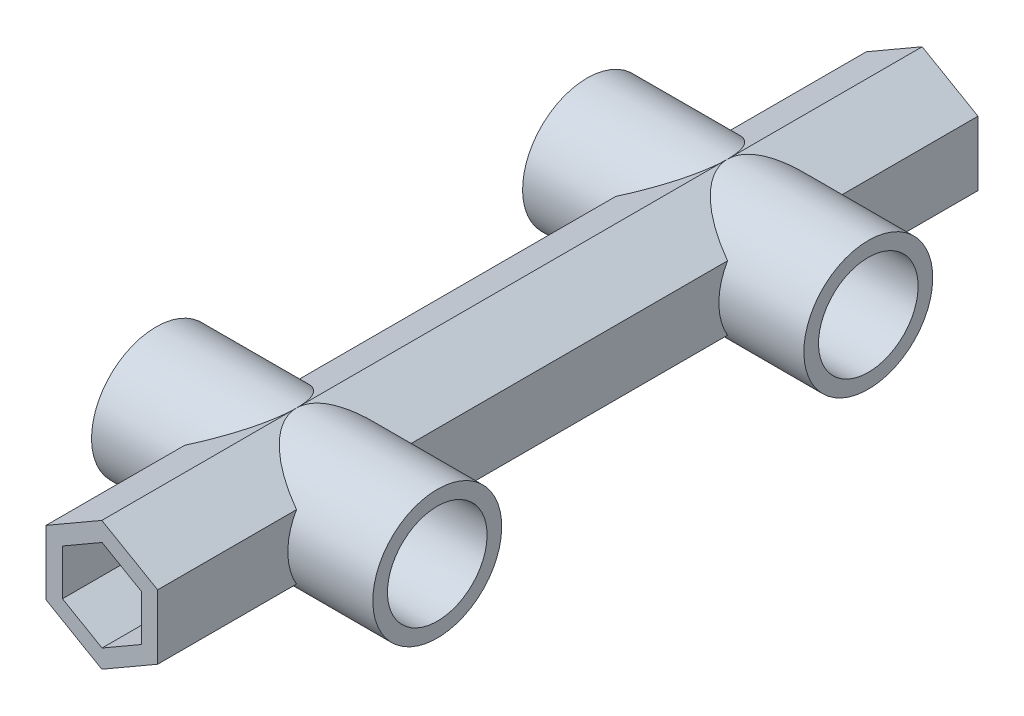
SolidWorks part; units mm, degrees
ref_plane "Front Plane" through (0, 0, 0) normal (0, 0, 1) x (1, 0, 0)
ref_plane "Top Plane" through (0, 0, 0) normal (0, 1, 0) x (1, 0, 0)
ref_plane "Right Plane" through (0, 0, 0) normal (1, 0, 0) x (0, 0, -1)
sketch "Sketch1" plane through (0, 0, 0) normal (0, 0, 1) x (1, 0, 0)
  line L1 (0, -11) -> (9.5263, -5.5)
  line L2 (9.5263, -5.5) -> (9.5263, 5.5)
  line L3 (9.5263, 5.5) -> (0, 11)
  line L4 (0, 11) -> (-9.5263, 5.5)
  line L5 (-9.5263, 5.5) -> (-9.5263, -5.5)
  line L6 (-9.5263, -5.5) -> (0, -11)
  circle A0 centre (0, 0) radius 11
  circle A1 centre (0, 0) radius 9.5263 construction
  circle A2 centre (0, 0) radius 6.4
  dimension "D1" = 22
  dimension "D2" = 12.8
extrude "Boss-Extrude1" [suppressed] add sketch "Sketch1" along normal mid plane 20 contours L4 A0 | L5 A0 | L5 L6 L1 L2 L3 L4 | L3 A0 | L2 A0 | L1 A0 | L6 A0
extrude "Boss-Extrude2" add sketch "Sketch1<3>" along normal mid plane 140 separate body contours L5 L6 L1 L2 L3 L4 A2 | A2 region at (-4.6176, -7.998, 0)
sketch "Sketch1<3>" plane through (0, 0, 0) normal (0, 0, 1) x (1, 0, 0) same geometry as "Sketch1"
sketch "Sketch10" plane through (0, 0, 70) normal (0, 0, 1) x (1, 0, 0)
  line L0 (0.0408, -7.8408) -> (6.7958, -3.9408)
  line L1 (6.7958, -3.9408) -> (6.7958, 3.8592)
  line L2 (6.7958, 3.8592) -> (0.0408, 7.7592)
  line L3 (0.0408, 7.7592) -> (-6.7142, 3.8592)
  line L4 (-6.7142, 3.8592) -> (-6.7142, -3.9408)
  line L5 (-6.7142, -3.9408) -> (0.0408, -7.8408)
  circle A0 centre (0.0408, -0.0408) radius 6.755 construction
  dimension "D1" = 15.6
extrude "Cut-Extrude6" cut sketch "Sketch10" against normal blind 15
sketch "Sketch11" plane through (0, 0, -70) normal (0, 0, -1) x (-1, 0, 0)
  line L0 (0, -7.8204) -> (6.755, -3.9204)
  line L1 (6.755, -3.9204) -> (6.755, 3.8796)
  line L2 (6.755, 3.8796) -> (0, 7.7796)
  line L3 (0, 7.7796) -> (-6.755, 3.8796)
  line L4 (-6.755, 3.8796) -> (-6.755, -3.9204)
  line L5 (-6.755, -3.9204) -> (0, -7.8204)
  circle A0 centre (0, -0.0204) radius 6.755 construction
  dimension "D1" = 15.6
extrude "Cut-Extrude7" cut sketch "Sketch11" against normal blind 15
sketch "Sketch3" plane through (9.5263, 0, 0) normal (1, 0, 0) x (0, 0, -1)
  line L0 (0, 5.5) -> (0, -5.5) construction
  line L1 (-70, 5.5) -> (70, 5.5) construction
  line L2 (-70, -5.5) -> (70, -5.5) construction
  line L3 (-70, -5.5) -> (-70, 5.5) construction
  circle A1 centre (-36.78, 0) radius 8.5
  circle A2 centre (36.78, 0) radius 8.5
  circle A3 centre (-36.78, 0) radius 11
  circle A4 centre (36.78, 0) radius 11
  dimension "D2" = 5.5
  dimension "D3" = 36.78
  dimension "D5" = 5.5
  dimension "D1" = 70
  dimension "D4" = 36.78
extrude "Boss-Extrude3" add sketch "Sketch3" along normal blind 14.5 and the other way blind 33.5
sketch "Sketch12" plane through (9.5263, 0, 0) normal (1, 0, 0) x (0, 0, -1)
  circle A0 centre (-36.78, 0) radius 8.5
  circle A1 centre (36.78, 0) radius 9
extrude "Cut-Extrude8" cut sketch "Sketch12" against normal through all
